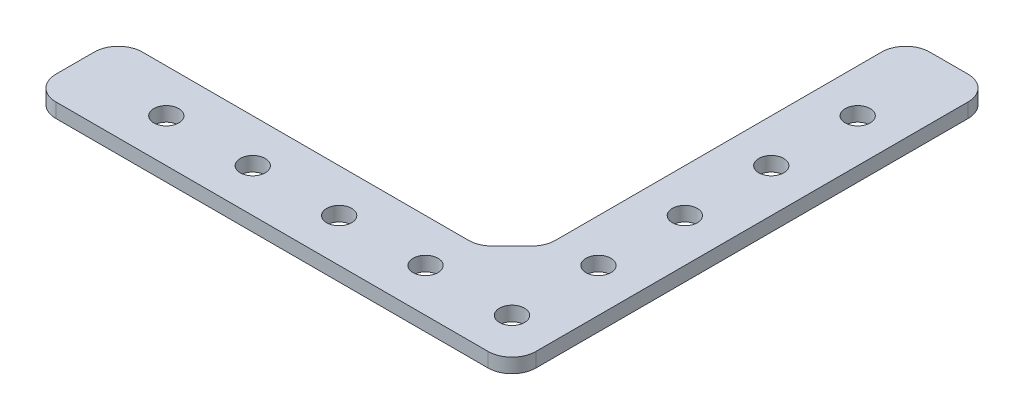
SolidWorks part; units mm, degrees
material "AISI 4340 Steel, annealed"
ref_plane "Front Plane" through (0, 0, 0) normal (0, 0, 1) x (1, 0, 0)
ref_plane "Top Plane" through (0, 0, 0) normal (0, 1, 0) x (1, 0, 0)
ref_plane "Right Plane" through (0, 0, 0) normal (1, 0, 0) x (0, 0, -1)
sketch "Sketch1" plane through (0, 0, 0) normal (0, 1, 0) x (1, 0, 0)
  line L1 (32, 50) -> (50, 50)
  line L2 (-50, -32) -> (-50, -50)
  line L3 (-50, -50) -> (50, -50)
  line L4 (50, 50) -> (50, -50)
  line L5 (16, -16) -> (50, -50) construction
  line L6 (-50, -50) -> (50, 50) construction
  line L7 (62.4476, -41) -> (-29.2217, -41) construction
  line L8 (32, 50) -> (32, -25)
  line L9 (41, 24.9633) -> (41, -68.659) construction
  line L10 (73.8742, -32) -> (-44.3096, -32) construction
  line L15 (32, -25) -> (25, -32)
  line L16 (25, -32) -> (-50, -32)
  line L17 (41, -41) -> (23, -41) construction
  line L18 (41, -41) -> (41, -23) construction
  circle A0 centre (41, -41) radius 2.6
  circle A7 centre (23, -41) radius 2.6
  circle A8 centre (5, -41) radius 2.6
  circle A9 centre (-13, -41) radius 2.6
  circle A10 centre (-31, -41) radius 2.6
  circle A13 centre (41, -23) radius 2.6
  circle A14 centre (41, -5) radius 2.6
  circle A15 centre (41, 13) radius 2.6
  circle A16 centre (41, 31) radius 2.6
  point P0 (0, 0)
  point P34 (32, 50)
  point P37 (-50, -32)
  dimension "D8" = 5.2
  dimension "D9" = 5
  dimension "D10" = 100
  dimension "D11" = 18
  dimension "D6" = 5
  dimension "D7" = 18
  dimension "D12" = 45
  dimension "D13" = 9
  dimension "D1" = 18
  dimension "D2" = 9
  dimension "D3" = 100
  dimension "D4" = 18
  dimension "D5" = 9
  dimension "D14" = 18
  dimension "D15" = 7
base flange "Base-Flange1" sketch "Sketch1" thickness 3 reverse thickness direction no parameters "D1"=3
fillet "Fillet1" radius 5 2 edges at (32, -1.5, 25) (25, -1.5, 32)
fillet "Fillet2" radius 5 5 edges at (50, -1.5, -50) (50, -1.5, 50) (-50, -1.5, 50) (32, -1.5, -50) (-50, -1.5, 32)
sketch "Bend-Lines1" [suppressed] plane through (0, 0, 0) normal (0, 1, 0) x (1, 0, 0)
sketch "Bounding-Box1" [suppressed] plane through (0, 0, 0) normal (0, 1, 0) x (1, 0, 0)
sheet metal parameters "Sheet-Metal4" thickness 3 parameters "D1"=3
flat pattern "Flat-Pattern4" [suppressed]
sketch "Bend-Lines2" plane through (0, 0, 0) normal (0, 1, 0) x (1, 0, 0)
sketch3d "Bounding-Box2" [suppressed]
  line L0 (-50, -50, 0) -> (50, -50, 0) construction
  line L1 (-50, 50, 0) -> (50, 50, 0) construction
  line L2 (-50, -50, 0) -> (-50, 50, 0) construction
  line L3 (50, -50, 0) -> (50, 50, 0) construction
